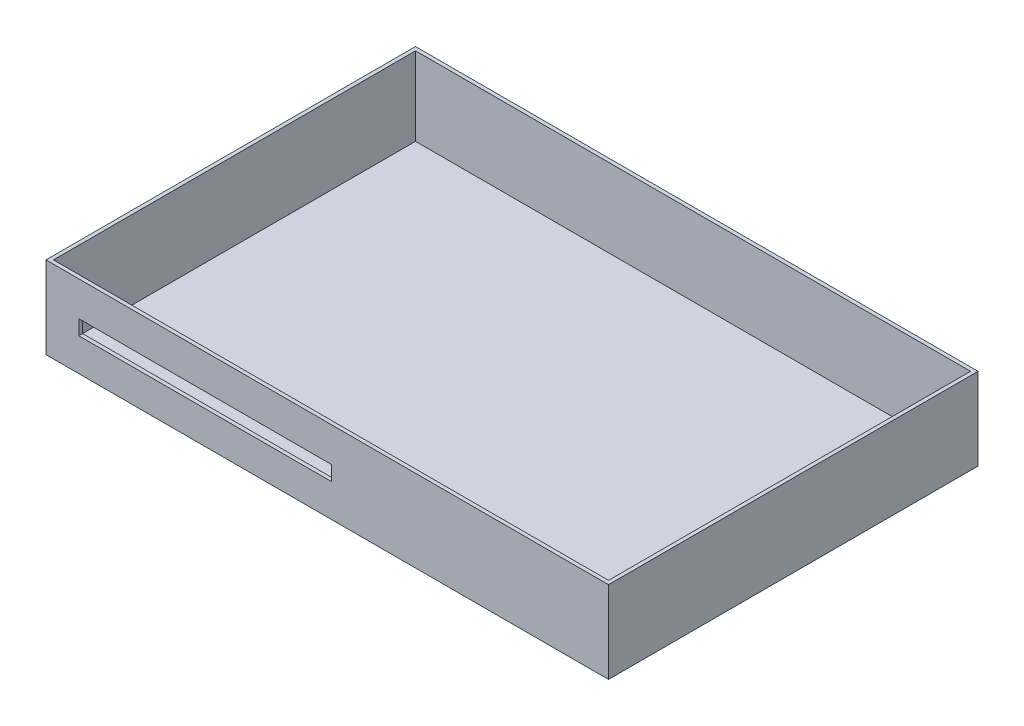
SolidWorks part; units mm, degrees
ref_plane "Front Plane" through (0, 0, 0) normal (0, 0, 1) x (1, 0, 0)
ref_plane "Top Plane" through (0, 0, 0) normal (0, 1, 0) x (1, 0, 0)
ref_plane "Right Plane" through (0, 0, 0) normal (1, 0, 0) x (0, 0, -1)
sketch "Sketch1" plane through (0, 0, 0) normal (0, 1, 0) x (1, 0, 0)
  line L1 (0, 0) -> (1370, 0)
  line L2 (0, 0) -> (0, 900)
  line L3 (0, 900) -> (1370, 900)
  line L4 (1370, 0) -> (1370, 900)
  dimension "D1" = 1370
  dimension "D2" = 900
extrude "Boss-Extrude1" add sketch "Sketch1" along normal blind 200
shell "Shell1" thickness 9 removed face at (685, 200, -450)
sketch "Sketch3" plane through (0, 0, 0) normal (0, 0, 1) x (1, 0, 0)
  line L1 (80, 116) -> (695, 116)
  line L2 (80, 116) -> (80, 80)
  line L3 (80, 80) -> (695, 80)
  line L4 (695, 116) -> (695, 80)
  dimension "D1" = 615
  dimension "D2" = 36
  dimension "D3" = 80
  dimension "D4" = 80
extrude "Cut-Extrude1" cut sketch "Sketch3" against normal up to next
